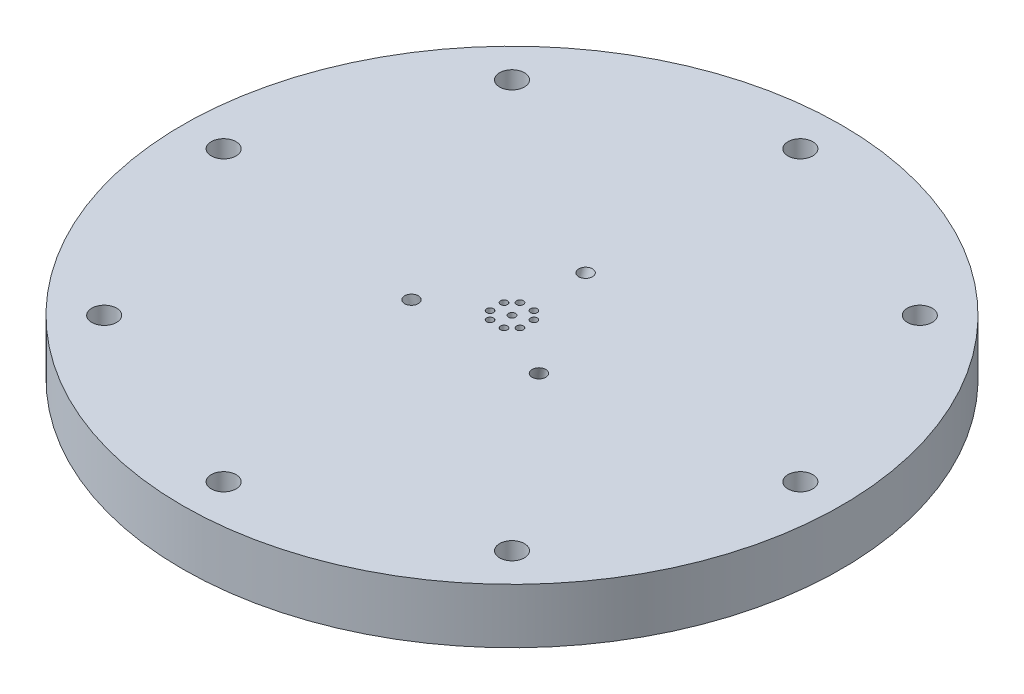
SolidWorks part; units mm, degrees
ref_plane "Front Plane" through (0, 0, 0) normal (0, 0, 1) x (1, 0, 0)
ref_plane "Top Plane" through (0, 0, 0) normal (0, 1, 0) x (1, 0, 0)
ref_plane "Right Plane" through (0, 0, 0) normal (1, 0, 0) x (0, 0, -1)
sketch "Sketch1" plane through (0, 0, 0) normal (0, 1, 0) x (1, 0, 0)
  circle A0 centre (0, 0) radius 38.1
  dimension "D1" = 76.2
extrude "Boss-Extrude1" add sketch "Sketch1" along normal blind 6.35
sketch "Sketch2" plane through (0, 0, 0) normal (0, -1, 0) x (1, 0, 0)
  circle A0 centre (0, 0) radius 33.3375
  circle A1 centre (0, 33.3375) radius 0.762
  dimension "D1" = 66.675
hole_wizard "CBORE for #4 Button Head Cap Screw1" positions "Sketch5" profile "Sketch4" counterbore size "#4" standard "ANSI Inch" end condition through all
sketch "Sketch5" plane through (0, 0, 0) normal (0, -1, 0) x (-1, 0, 0)
  point P0 (0, -33.3375)
sketch "Sketch4" plane through (0, 0, 33.3375) normal (1, 0, 0) x (0, 0, -1)
  line L0 (0, 0) -> (0, 6.35)
  line L1 (0, 6.35) -> (1.4351, 6.35)
  line L3 (1.4351, 6.35) -> (1.4351, 3.175)
  line L4 (1.4351, 3.175) -> (2.413, 3.175)
  line L5 (2.413, 3.175) -> (2.413, 0)
  line L7 (2.413, 0) -> (0, 0)
  line L11 (0, -6.35) -> (0, 107.95) construction
  dimension "Thru Hole Dia." = 2.8702
  dimension "Thru Hole Depth" = 6.35
  dimension "C'Bore Dia." = 4.826
  dimension "C'Bore Depth" = 3.175
pattern_circular "CirPattern1" count 8 over 360 about axis through (0, 0, 0) along (0, 1, 0) of "CBORE for #4 Button Head Cap Screw1"
sketch "Sketch6" plane through (0, 0, 0) normal (0, -1, 0) x (1, 0, 0)
  line L0 (16.6063, 0) -> (-10.7831, 0) construction
  line L1 (0, 0) -> (0, -21.5639) construction
  line L2 (0, 0) -> (8.6721, -4.0439) construction
  line L3 (0, 0) -> (1.6102, -3.453) construction
  circle A0 centre (0.8051, -1.7265) radius 0.3969
  circle A1 centre (1.7265, -0.8051) radius 0.3969
  circle A2 centre (0, 0) radius 0.3969
  circle A3 centre (0, -6.35) radius 0.7938
  dimension "D1" = 6.35
extrude "Cut-Extrude1" cut sketch "Sketch6" against normal through all contours A0 | A1
pattern_circular "CirPattern2" count 4 over 360 about axis through (0, 0, 0) along (0, -1, 0) of "Cut-Extrude1"
extrude "Cut-Extrude2" cut sketch "Sketch6<3>" against normal through all contours A2
sketch "Sketch6<3>" plane through (0, 0, 0) normal (0, -1, 0) x (1, 0, 0) same geometry as "Sketch6"
sketch "Sketch8" plane through (0, 6.35, 0) normal (0, 1, 0) x (1, 0, 0)
  line L0 (0, 0) -> (0, 13.3258) construction
  circle A0 centre (0, 8.509) radius 0.7937
  dimension "D1" = 1.5875
  dimension "D2" = 8.509
sketch3d "3DSketch2"
  line L0 (0, 6.35, -8.509) -> (0, 0, -6.35)
sweep "Cut-Sweep2" cut profiles "Sketch8" path "3DSketch2"
pattern_circular "CirPattern4" count 3 over 360 about axis through (0, 6.35, 0) along (0, -1, 0) of "Cut-Sweep2"
